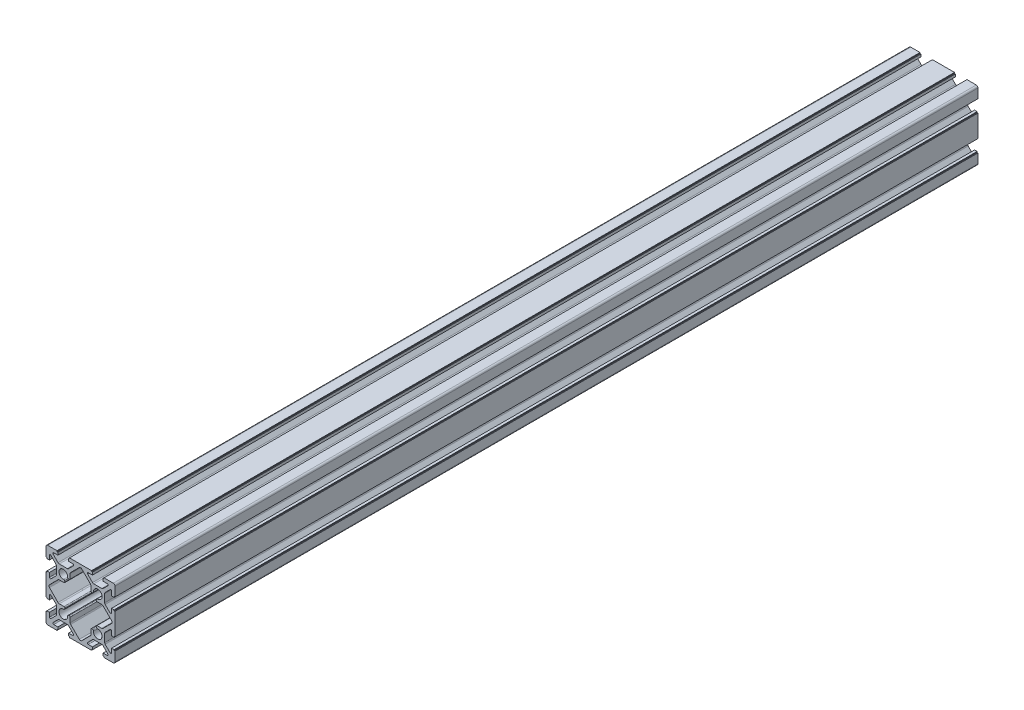
SolidWorks part; units mm, degrees
ref_plane "前视基准面" through (0, 0, 0) normal (0, 0, 1) x (1, 0, 0)
ref_plane "上视基准面" through (0, 0, 0) normal (0, 1, 0) x (1, 0, 0)
ref_plane "右视基准面" through (0, 0, 0) normal (1, 0, 0) x (0, 0, -1)
sketch "草图1" plane through (0, 0, 0) normal (0, 0, 1) x (1, 0, 0)
  line L0 (31.4283, 33.0307) -> (31.2907, 33.5441)
  line L1 (28.8233, 31.0766) -> (29.3366, 30.9391)
  line L2 (28.1939, 27.8605) -> (28.1939, 30.5937)
  line L3 (22.901, 22.1534) -> (27.901, 27.1534)
  line L4 (16.4868, 27.1534) -> (21.4868, 22.1534)
  line L5 (16.1939, 30.5937) -> (16.1939, 27.8605)
  line L6 (15.0511, 30.9391) -> (15.5645, 31.0766)
  line L7 (13.097, 33.5441) -> (12.9595, 33.0307)
  line L8 (9.8809, 34.1735) -> (12.6141, 34.1735)
  line L9 (4.1738, 39.4664) -> (9.1738, 34.4664)
  line L10 (9.1738, 45.8806) -> (4.1738, 40.8806)
  line L11 (12.6141, 46.1735) -> (9.8809, 46.1735)
  line L12 (12.9595, 47.3162) -> (13.097, 46.8029)
  line L13 (15.5645, 49.2703) -> (15.0511, 49.4079)
  line L14 (16.1939, 52.4865) -> (16.1939, 49.7533)
  line L15 (21.4868, 58.1936) -> (16.4868, 53.1936)
  line L16 (27.901, 53.1936) -> (22.901, 58.1936)
  line L17 (28.1939, 49.7533) -> (28.1939, 52.4865)
  line L18 (29.3366, 49.4079) -> (28.8233, 49.2703)
  line L19 (31.2907, 46.8029) -> (31.4283, 47.3162)
  line L20 (34.5069, 46.1735) -> (31.7737, 46.1735)
  line L21 (40.214, 40.8806) -> (35.214, 45.8806)
  line L22 (35.214, 34.4664) -> (40.214, 39.4664)
  line L23 (31.7737, 34.1735) -> (34.5069, 34.1735)
  line L24 (29.1738, 25.8806) -> (26.3202, 23.027)
  line L25 (34.5069, 26.1735) -> (29.8809, 26.1735)
  line L26 (38.0675, 23.027) -> (35.214, 25.8806)
  line L27 (35.2939, 22.1735) -> (37.714, 22.1735)
  line L28 (35.2939, 20.6735) -> (35.2939, 22.1735)
  line L29 (35.7939, 20.6735) -> (35.2939, 20.6735)
  line L30 (35.7939, 20.1735) -> (35.7939, 20.6735)
  line L31 (41.1939, 20.1735) -> (35.7939, 20.1735)
  line L32 (42.1939, 26.5735) -> (42.1939, 21.1735)
  line L33 (41.6939, 26.5735) -> (42.1939, 26.5735)
  line L34 (41.6939, 27.0735) -> (41.6939, 26.5735)
  line L35 (40.1939, 27.0735) -> (41.6939, 27.0735)
  line L36 (40.1939, 24.6534) -> (40.1939, 27.0735)
  line L37 (36.4868, 27.1534) -> (39.3403, 24.2998)
  line L38 (36.1939, 32.4865) -> (36.1939, 27.8605)
  line L39 (39.3403, 36.0471) -> (36.4868, 33.1936)
  line L40 (40.1939, 33.2735) -> (40.1939, 35.6936)
  line L41 (41.6939, 33.2735) -> (40.1939, 33.2735)
  line L42 (41.6939, 33.7735) -> (41.6939, 33.2735)
  line L43 (42.1939, 33.7735) -> (41.6939, 33.7735)
  line L44 (42.1939, 46.5735) -> (42.1939, 33.7735)
  line L45 (41.6939, 46.5735) -> (42.1939, 46.5735)
  line L46 (41.6939, 47.0735) -> (41.6939, 46.5735)
  line L47 (40.1939, 47.0735) -> (41.6939, 47.0735)
  line L48 (40.1939, 44.6534) -> (40.1939, 47.0735)
  line L49 (36.4868, 47.1534) -> (39.3403, 44.2998)
  line L50 (36.1939, 52.4865) -> (36.1939, 47.8605)
  line L51 (39.3403, 56.0471) -> (36.4868, 53.1936)
  line L52 (40.1939, 53.2735) -> (40.1939, 55.6936)
  line L53 (41.6939, 53.2735) -> (40.1939, 53.2735)
  line L54 (41.6939, 53.7735) -> (41.6939, 53.2735)
  line L55 (42.1939, 53.7735) -> (41.6939, 53.7735)
  line L56 (42.1939, 59.1735) -> (42.1939, 53.7735)
  line L57 (35.7939, 60.1735) -> (41.1939, 60.1735)
  line L58 (35.7939, 59.6735) -> (35.7939, 60.1735)
  line L59 (35.2939, 59.6735) -> (35.7939, 59.6735)
  line L60 (35.2939, 58.1735) -> (35.2939, 59.6735)
  line L61 (37.714, 58.1735) -> (35.2939, 58.1735)
  line L62 (35.214, 54.4664) -> (38.0675, 57.3199)
  line L63 (29.8809, 54.1735) -> (34.5069, 54.1735)
  line L64 (26.3202, 57.3199) -> (29.1738, 54.4664)
  line L65 (29.0939, 58.1735) -> (26.6738, 58.1735)
  line L66 (29.0939, 59.6735) -> (29.0939, 58.1735)
  line L67 (28.5939, 59.6735) -> (29.0939, 59.6735)
  line L68 (28.5939, 60.1735) -> (28.5939, 59.6735)
  line L69 (15.7939, 60.1735) -> (28.5939, 60.1735)
  line L70 (15.7939, 59.6735) -> (15.7939, 60.1735)
  line L71 (15.2939, 59.6735) -> (15.7939, 59.6735)
  line L72 (15.2939, 58.1735) -> (15.2939, 59.6735)
  line L73 (17.714, 58.1735) -> (15.2939, 58.1735)
  line L74 (15.214, 54.4664) -> (18.0675, 57.3199)
  line L75 (9.8809, 54.1735) -> (14.5069, 54.1735)
  line L76 (6.3202, 57.3199) -> (9.1738, 54.4664)
  line L77 (9.0939, 58.1735) -> (6.6738, 58.1735)
  line L78 (9.0939, 59.6735) -> (9.0939, 58.1735)
  line L79 (8.5939, 59.6735) -> (9.0939, 59.6735)
  line L80 (8.5939, 60.1735) -> (8.5939, 59.6735)
  line L81 (3.1939, 60.1735) -> (8.5939, 60.1735)
  line L82 (2.1939, 53.7735) -> (2.1939, 59.1735)
  line L83 (2.6939, 53.7735) -> (2.1939, 53.7735)
  line L84 (2.6939, 53.2735) -> (2.6939, 53.7735)
  line L85 (4.1939, 53.2735) -> (2.6939, 53.2735)
  line L86 (4.1939, 55.6936) -> (4.1939, 53.2735)
  line L87 (7.901, 53.1936) -> (5.0474, 56.0471)
  line L88 (8.1939, 47.8605) -> (8.1939, 52.4865)
  line L89 (5.0474, 44.2998) -> (7.901, 47.1534)
  line L90 (4.1939, 47.0735) -> (4.1939, 44.6534)
  line L91 (2.6939, 47.0735) -> (4.1939, 47.0735)
  line L92 (2.6939, 46.5735) -> (2.6939, 47.0735)
  line L93 (2.1939, 46.5735) -> (2.6939, 46.5735)
  line L94 (2.1939, 33.7735) -> (2.1939, 46.5735)
  line L95 (2.6939, 33.7735) -> (2.1939, 33.7735)
  line L96 (2.6939, 33.2735) -> (2.6939, 33.7735)
  line L97 (4.1939, 33.2735) -> (2.6939, 33.2735)
  line L98 (4.1939, 35.6936) -> (4.1939, 33.2735)
  line L99 (7.901, 33.1936) -> (5.0474, 36.0471)
  line L100 (8.1939, 27.8605) -> (8.1939, 32.4865)
  line L101 (5.0474, 24.2998) -> (7.901, 27.1534)
  line L102 (4.1939, 27.0735) -> (4.1939, 24.6534)
  line L103 (2.6939, 27.0735) -> (4.1939, 27.0735)
  line L104 (2.6939, 26.5735) -> (2.6939, 27.0735)
  line L105 (2.1939, 26.5735) -> (2.6939, 26.5735)
  line L106 (2.1939, 21.1735) -> (2.1939, 26.5735)
  line L107 (8.5939, 20.1735) -> (3.1939, 20.1735)
  line L108 (8.5939, 20.6735) -> (8.5939, 20.1735)
  line L109 (9.0939, 20.6735) -> (8.5939, 20.6735)
  line L110 (9.0939, 22.1735) -> (9.0939, 20.6735)
  line L111 (6.6738, 22.1735) -> (9.0939, 22.1735)
  line L112 (9.1738, 25.8806) -> (6.3202, 23.027)
  line L113 (14.5069, 26.1735) -> (9.8809, 26.1735)
  line L114 (18.0675, 23.027) -> (15.214, 25.8806)
  line L115 (15.2939, 22.1735) -> (17.714, 22.1735)
  line L116 (15.2939, 20.6735) -> (15.2939, 22.1735)
  line L117 (15.7939, 20.6735) -> (15.2939, 20.6735)
  line L118 (15.7939, 20.1735) -> (15.7939, 20.6735)
  line L119 (28.5939, 20.1735) -> (15.7939, 20.1735)
  line L120 (28.5939, 20.6735) -> (28.5939, 20.1735)
  line L121 (29.0939, 20.6735) -> (28.5939, 20.6735)
  line L122 (29.0939, 22.1735) -> (29.0939, 20.6735)
  line L123 (26.6738, 22.1735) -> (29.0939, 22.1735)
  arc A0 (31.4283, 33.0307) -> (31.9584, 32.6623) centre (31.9112, 33.1601) ccw
  arc A1 (29.705, 30.409) -> (31.9584, 32.6623) centre (32.1939, 30.1735) ccw
  arc A2 (29.705, 30.409) -> (29.3366, 30.9391) centre (29.2072, 30.4561) ccw
  arc A3 (28.8233, 31.0766) -> (28.1939, 30.5937) centre (28.6939, 30.5937) ccw
  arc A4 (27.901, 27.1534) -> (28.1939, 27.8605) centre (27.1939, 27.8605) ccw
  arc A5 (21.4868, 22.1534) -> (22.901, 22.1534) centre (22.1939, 22.8605) ccw
  arc A6 (16.1939, 27.8605) -> (16.4868, 27.1534) centre (17.1939, 27.8605) ccw
  arc A7 (16.1939, 30.5937) -> (15.5645, 31.0766) centre (15.6939, 30.5937) ccw
  arc A8 (15.0511, 30.9391) -> (14.6828, 30.409) centre (15.1805, 30.4561) ccw
  arc A9 (12.4294, 32.6623) -> (14.6828, 30.409) centre (12.1939, 30.1735) ccw
  arc A10 (12.4294, 32.6623) -> (12.9595, 33.0307) centre (12.4765, 33.1601) ccw
  arc A11 (13.097, 33.5441) -> (12.6141, 34.1735) centre (12.6141, 33.6735) ccw
  arc A12 (9.1738, 34.4664) -> (9.8809, 34.1735) centre (9.8809, 35.1735) ccw
  arc A13 (4.1738, 40.8806) -> (4.1738, 39.4664) centre (4.8809, 40.1735) ccw
  arc A14 (9.8809, 46.1735) -> (9.1738, 45.8806) centre (9.8809, 45.1735) ccw
  arc A15 (12.6141, 46.1735) -> (13.097, 46.8029) centre (12.6141, 46.6735) ccw
  arc A16 (12.9595, 47.3162) -> (12.4294, 47.6846) centre (12.4765, 47.1868) ccw
  arc A17 (14.6828, 49.9379) -> (12.4294, 47.6846) centre (12.1939, 50.1735) ccw
  arc A18 (14.6828, 49.9379) -> (15.0511, 49.4079) centre (15.1805, 49.8908) ccw
  arc A19 (15.5645, 49.2703) -> (16.1939, 49.7533) centre (15.6939, 49.7533) ccw
  arc A20 (16.4868, 53.1936) -> (16.1939, 52.4865) centre (17.1939, 52.4865) ccw
  arc A21 (22.901, 58.1936) -> (21.4868, 58.1936) centre (22.1939, 57.4865) ccw
  arc A22 (28.1939, 52.4865) -> (27.901, 53.1936) centre (27.1939, 52.4865) ccw
  arc A23 (28.1939, 49.7533) -> (28.8233, 49.2703) centre (28.6939, 49.7533) ccw
  arc A24 (29.3366, 49.4079) -> (29.705, 49.9379) centre (29.2072, 49.8908) ccw
  arc A25 (31.9584, 47.6846) -> (29.705, 49.9379) centre (32.1939, 50.1735) ccw
  arc A26 (31.9584, 47.6846) -> (31.4283, 47.3162) centre (31.9112, 47.1868) ccw
  arc A27 (31.2907, 46.8029) -> (31.7737, 46.1735) centre (31.7737, 46.6735) ccw
  arc A28 (35.214, 45.8806) -> (34.5069, 46.1735) centre (34.5069, 45.1735) ccw
  arc A29 (40.214, 39.4664) -> (40.214, 40.8806) centre (39.5069, 40.1735) ccw
  arc A30 (34.5069, 34.1735) -> (35.214, 34.4664) centre (34.5069, 35.1735) ccw
  arc A31 (31.7737, 34.1735) -> (31.2907, 33.5441) centre (31.7737, 33.6735) ccw
  arc A32 (26.3202, 23.027) -> (26.6738, 22.1735) centre (26.6738, 22.6735) ccw
  arc A33 (29.8809, 26.1735) -> (29.1738, 25.8806) centre (29.8809, 25.1735) ccw
  arc A34 (35.214, 25.8806) -> (34.5069, 26.1735) centre (34.5069, 25.1735) ccw
  arc A35 (37.714, 22.1735) -> (38.0675, 23.027) centre (37.714, 22.6735) ccw
  arc A36 (41.1939, 20.1735) -> (42.1939, 21.1735) centre (41.1939, 21.1735) ccw
  arc A37 (39.3403, 24.2998) -> (40.1939, 24.6534) centre (39.6939, 24.6534) ccw
  arc A38 (36.1939, 27.8605) -> (36.4868, 27.1534) centre (37.1939, 27.8605) ccw
  arc A39 (36.4868, 33.1936) -> (36.1939, 32.4865) centre (37.1939, 32.4865) ccw
  arc A40 (40.1939, 35.6936) -> (39.3403, 36.0471) centre (39.6939, 35.6936) ccw
  arc A41 (39.3403, 44.2998) -> (40.1939, 44.6534) centre (39.6939, 44.6534) ccw
  arc A42 (36.1939, 47.8605) -> (36.4868, 47.1534) centre (37.1939, 47.8605) ccw
  arc A43 (36.4868, 53.1936) -> (36.1939, 52.4865) centre (37.1939, 52.4865) ccw
  arc A44 (40.1939, 55.6936) -> (39.3403, 56.0471) centre (39.6939, 55.6936) ccw
  arc A45 (42.1939, 59.1735) -> (41.1939, 60.1735) centre (41.1939, 59.1735) ccw
  arc A46 (38.0675, 57.3199) -> (37.714, 58.1735) centre (37.714, 57.6735) ccw
  arc A47 (34.5069, 54.1735) -> (35.214, 54.4664) centre (34.5069, 55.1735) ccw
  arc A48 (29.1738, 54.4664) -> (29.8809, 54.1735) centre (29.8809, 55.1735) ccw
  arc A49 (26.6738, 58.1735) -> (26.3202, 57.3199) centre (26.6738, 57.6735) ccw
  arc A50 (18.0675, 57.3199) -> (17.714, 58.1735) centre (17.714, 57.6735) ccw
  arc A51 (14.5069, 54.1735) -> (15.214, 54.4664) centre (14.5069, 55.1735) ccw
  arc A52 (9.1738, 54.4664) -> (9.8809, 54.1735) centre (9.8809, 55.1735) ccw
  arc A53 (6.6738, 58.1735) -> (6.3202, 57.3199) centre (6.6738, 57.6735) ccw
  arc A54 (3.1939, 60.1735) -> (2.1939, 59.1735) centre (3.1939, 59.1735) ccw
  arc A55 (5.0474, 56.0471) -> (4.1939, 55.6936) centre (4.6939, 55.6936) ccw
  arc A56 (8.1939, 52.4865) -> (7.901, 53.1936) centre (7.1939, 52.4865) ccw
  arc A57 (7.901, 47.1534) -> (8.1939, 47.8605) centre (7.1939, 47.8605) ccw
  arc A58 (4.1939, 44.6534) -> (5.0474, 44.2998) centre (4.6939, 44.6534) ccw
  arc A59 (5.0474, 36.0471) -> (4.1939, 35.6936) centre (4.6939, 35.6936) ccw
  arc A60 (8.1939, 32.4865) -> (7.901, 33.1936) centre (7.1939, 32.4865) ccw
  arc A61 (7.901, 27.1534) -> (8.1939, 27.8605) centre (7.1939, 27.8605) ccw
  arc A62 (4.1939, 24.6534) -> (5.0474, 24.2998) centre (4.6939, 24.6534) ccw
  arc A63 (2.1939, 21.1735) -> (3.1939, 20.1735) centre (3.1939, 21.1735) ccw
  arc A64 (6.3202, 23.027) -> (6.6738, 22.1735) centre (6.6738, 22.6735) ccw
  arc A65 (9.8809, 26.1735) -> (9.1738, 25.8806) centre (9.8809, 25.1735) ccw
  arc A66 (15.214, 25.8806) -> (14.5069, 26.1735) centre (14.5069, 25.1735) ccw
  arc A67 (17.714, 22.1735) -> (18.0675, 23.027) centre (17.714, 22.6735) ccw
extrude "拉伸1" add sketch "草图1" along normal blind 500
